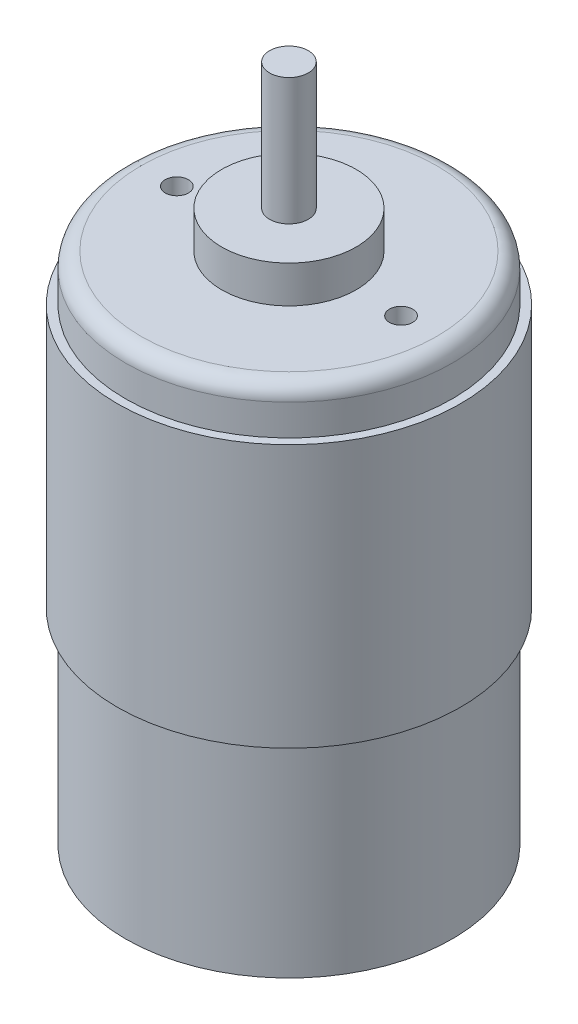
SolidWorks part; units mm, degrees
ref_plane "Front Plane" through (0, 0, 0) normal (0, 0, 1) x (1, 0, 0)
ref_plane "Top Plane" through (0, 0, 0) normal (0, 1, 0) x (1, 0, 0)
ref_plane "Right Plane" through (0, 0, 0) normal (1, 0, 0) x (0, 0, -1)
sketch "Sketch1" plane through (0, 0, 0) normal (0, 1, 0) x (1, 0, 0)
  circle A0 centre (0, 0) radius 21.125
extrude "Boss-Extrude1" add sketch "Sketch1" along normal blind 66.5
sketch "Sketch2" plane through (0, 0, 0) normal (0, -1, 0) x (1, 0, 0)
  circle A0 centre (0, 0) radius 7.2
extrude "Boss-Extrude2" add sketch "Sketch2" along normal blind 4
sketch "Sketch3" plane through (0, -4, 0) normal (0, -1, 0) x (1, 0, 0)
  circle A0 centre (0, 0) radius 2.5
extrude "Boss-Extrude3" add sketch "Sketch3" along normal blind 6.2
sketch "Sketch4" plane through (0, 66.5, 0) normal (0, 1, 0) x (1, 0, 0)
  circle A0 centre (0, 0) radius 8.7
extrude "Boss-Extrude4" add sketch "Sketch4" along normal blind 4.8
sketch "Sketch5" plane through (0, 71.3, 0) normal (0, 1, 0) x (1, 0, 0)
  circle A0 centre (0, 0) radius 2.5
extrude "Boss-Extrude5" add sketch "Sketch5" along normal blind 16.4
sketch "Sketch6" plane through (0, 66.5, 0) normal (0, 1, 0) x (1, 0, 0)
  line L0 (0, 0) -> (14.5, 0)
  line L1 (0, 0) -> (0, 6.8536)
  circle A0 centre (14.5, 0) radius 1.5
  circle A1 centre (-14.5, 0) radius 1.5
extrude "Cut-Extrude1" cut sketch "Sketch6" against normal blind 5 contours A0 | A1 region at (14.5, 66.5, 1.4576) region at (-14.5, 66.5, 0)
sketch "Sketch7" plane through (0, 66.5, 0) normal (0, 1, 0) x (1, 0, 0)
  line L1 (1.25, 21.088) -> (1.25, 22.1648)
  line L2 (-1.25, 21.088) -> (-1.25, 22.1648)
  arc A0 (-1.25, 22.1648) -> (1.25, 22.1648) centre (0, 0) ccw
  circle A1 centre (0, 0) radius 21.125 construction
  arc A2 (-1.25, 21.088) -> (1.25, 21.088) centre (0, 0) ccw
extrude "Boss-Extrude6" add sketch "Sketch7" against normal blind 40
extrude "Cut-Extrude2" cut sketch "Sketch7<3>" against normal blind 6
sketch "Sketch7<3>" plane through (0, 66.5, 0) normal (0, 1, 0) x (1, 0, 0) same geometry as "Sketch7"
fillet "Fillet1" radius 2 1 edges at (0, 66.5, 21.125)
